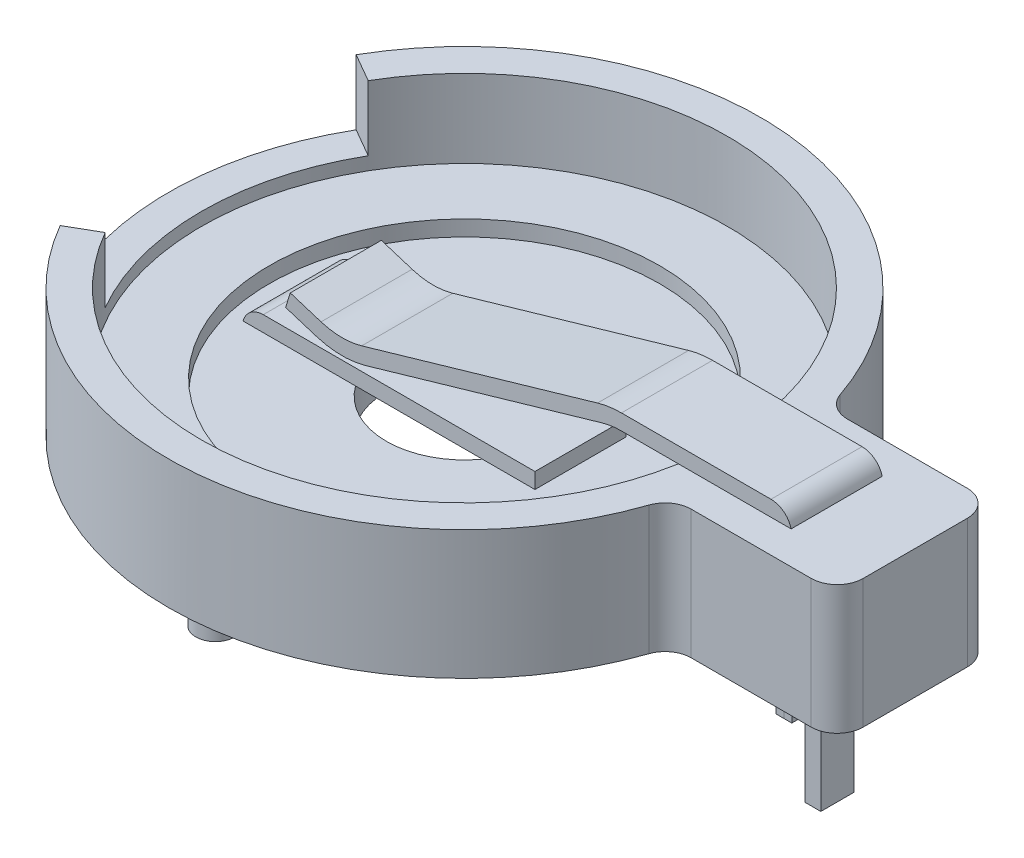
SolidWorks part; units mm, degrees
ref_plane "Front" through (0, 0, 0) normal (0, 0, 1) x (1, 0, 0)
ref_plane "Top" through (0, 0, 0) normal (0, 1, 0) x (1, 0, 0)
ref_plane "Right" through (0, 0, 0) normal (1, 0, 0) x (0, 0, -1)
sketch "Эскиз1" plane through (0, 0, 0) normal (0, 1, 0) x (1, 0, 0)
  line L0 (-11.375, 0) -> (17.5213, 0) construction
  line L1 (11.7107, 3) -> (16.325, 3)
  line L2 (11.7107, -3) -> (16.325, -3)
  line L3 (17.325, 2) -> (17.325, -2)
  arc A0 (16.325, 3) -> (17.325, 2) centre (16.325, 2) cw
  arc A2 (10.7644, 3.6768) -> (10.7644, -3.6768) centre (0, 0) ccw
  arc A3 (16.325, -3) -> (17.325, -2) centre (16.325, -2) ccw
  arc A4 (11.7107, 3) -> (10.7644, 3.6768) centre (11.7107, 4) cw
  arc A5 (11.7107, -3) -> (10.7644, -3.6768) centre (11.7107, -4) ccw
  point P11 (17.325, 3)
  point P14 (17.325, -3)
  point P17 (10.9723, 3)
  point P20 (10.9723, -3)
  dimension "D1" = 11.375
  dimension "D5" = 1
  dimension "D3" = 6
  dimension "D4" = 28.7
extrude "Вытянуть1" add sketch "Эскиз1" along normal blind 4.95
sketch "Эскиз2" plane through (0, 4.95, 0) normal (0, 1, 0) x (-1, 0, 0)
  circle A0 centre (0, 0) radius 10.11
  dimension "D1" = 20.22
extrude "Вырез-Вытянуть1" cut sketch "Эскиз2" against normal blind 3
sketch "Эскиз3" plane through (0, 4.95, 0) normal (0, 1, 0) x (-1, 0, 0)
  line L0 (0, 0) -> (11.375, 0) construction
  line L1 (0, 0) -> (11.3365, -6.5451) construction
  line L2 (0, 0) -> (11.3365, 6.5451) construction
  line L3 (8.7555, -5.055) -> (9.851, -5.6875)
  line L4 (9.851, 5.6875) -> (8.7555, 5.055)
  arc A0 (-10.7644, -3.6768) -> (-10.7644, 3.6768) centre (0, 0) ccw construction
  arc A1 (8.7555, 5.055) -> (8.7555, -5.055) centre (0, 0) cw
  circle A2 centre (0, 0) radius 10.11 construction
  arc A3 (9.851, 5.6875) -> (9.851, -5.6875) centre (0, 0) cw
  dimension "D1" = 30
extrude "Вырез-Вытянуть2" cut sketch "Эскиз3" against normal blind 2.5
sketch "Эскиз4" plane through (0, 1.95, 0) normal (0, 1, 0) x (-1, 0, 0)
  circle A0 centre (0, 0) radius 7.5
  dimension "D1" = 15
extrude "Вырез-Вытянуть3" cut sketch "Эскиз4" against normal blind 0.6
sketch "Эскиз5" plane through (0, 1.35, 0) normal (0, 1, 0) x (-1, 0, 0)
  circle A0 centre (0, 0) radius 3
extrude "Вырез-Вытянуть4" cut sketch "Эскиз5" against normal up to next
ref_plane "Плоскость1" through (0, 0, 0) normal (0, 0, 1) x (1, 0, 0)
sketch "Эскиз7" plane through (0, 0, 0) normal (0, 0, 1) x (1, 0, 0)
  line L0 (-7.9171, 1.65) -> (-0.6324, 1.65) construction
  line L1 (7.5, 1.35) -> (-7.5, 1.35) construction
  line L2 (-6.4821, 1.15) -> (-6.4821, -5)
  line L4 (-5.9821, 1.65) -> (4.4584, 1.65)
  line L6 (-11.375, 0) -> (10.7644, 0) construction
  arc A0 (-6.4821, 1.15) -> (-5.9821, 1.65) centre (-5.9821, 1.15) cw
  point P12 (-6.4821, 1.65)
  dimension "D3" = 0.5
  dimension "D1" = 5
  dimension "D2" = 0.3
ref_plane "Плоскость2" through (4.4584, 0, 0) normal (1, 0, 0) x (0, 0, -1)
sketch "Эскиз8" plane through (4.4584, 0, 0) normal (1, 0, 0) x (0, 0, -1)
  line L0 (-1.75, 1.95) -> (1.75, 1.95)
  line L1 (-1.75, 1.95) -> (-1.75, 1.35)
  line L2 (7.5, 1.95) -> (-7.5, 1.95) construction
  line L3 (3, 1.35) -> (-3, 1.35) construction
  line L4 (0, 7.1854) -> (0, -7.1854) construction
  line L6 (10.11, 1.95) -> (-10.11, 1.95) construction
  line L7 (-1.75, 1.35) -> (1.75, 1.35)
  line L8 (0, 2.6946) -> (0, 0.3193) construction
  line L9 (0, 1.15) -> (0, -5) construction
  line L10 (1.75, 1.95) -> (1.75, 1.35)
  point P18 (0, 1.35)
  point P19 (0, 1.95)
  dimension "D1" = 1.75
sweep "По траектории2" add profiles "Эскиз8" path "Эскиз7"
sketch "Эскиз9" plane through (0, 0, 0) normal (0, -1, 0) x (1, 0, 0)
  line L0 (0, 11.375) -> (0, 0) construction
  line L1 (0, 0) -> (9.851, -5.6875) construction
  line L2 (0, 0) -> (-9.851, -5.6875) construction
  arc A0 (10.7644, 3.6768) -> (10.7644, -3.6768) centre (0, 0) ccw construction
  circle A1 centre (0, 0) radius 9.575 construction
  circle A2 centre (0, 9.575) radius 0.75
  circle A3 centre (8.2922, -4.7875) radius 0.75
  circle A4 centre (-8.2922, -4.7875) radius 0.75
  dimension "D3" = 1.8
  dimension "D1" = 120
  dimension "D2" = 120
extrude "Вытянуть2" add sketch "Эскиз9" along normal blind 1.5
sketch "Эскиз10" plane through (0, -5, 0) normal (0, -1, 0) x (1, 0, 0)
  line L0 (-6.7821, 0) -> (-6.1821, 0) construction
  line L1 (-6.7821, -1.75) -> (-6.7821, 1.75) construction
  line L2 (-6.1821, 1.75) -> (-6.1821, -1.75) construction
  line L3 (-6.7821, 1.75) -> (-6.7821, 0.635)
  line L4 (-6.7821, -1.75) -> (-6.1821, -1.75)
  line L5 (-6.7821, -1.75) -> (-6.7821, -0.635)
  line L6 (-6.7821, -0.635) -> (-6.1821, -0.635)
  line L7 (-6.1821, -1.75) -> (-6.1821, -0.635)
  line L8 (-6.7821, 1.75) -> (-6.1821, 1.75)
  line L9 (-6.1821, 1.75) -> (-6.1821, 0.635)
  line L10 (-6.7821, 0.635) -> (-6.1821, 0.635)
  dimension "D1" = 1.27
extrude "Вырез-Вытянуть5" cut sketch "Эскиз10" against normal blind 3.5
ref_plane "Плоскость3" through (0, -5, 0) normal (0, -1, 0) x (1, 0, 0)
sketch "Эскиз12" plane through (0, 0, 0) normal (0, 0, 1) x (1, 0, 0)
  line L0 (14.0179, 0) -> (14.0179, 4.75)
  line L1 (11.7107, 4.95) -> (16.325, 4.95) construction
  line L2 (13.5179, 5.25) -> (7.7703, 5.25)
  line L3 (-6.4022, 2.25) -> (2.5235, 2.25) construction
  line L4 (-5.9821, 1.95) -> (4.4584, 1.95) construction
  line L5 (6.9347, 5.1313) -> (-2.1288, 2.5027)
  line L6 (-3.8652, 2.5223) -> (-5.0477, 2.8946)
  line L7 (11.7107, 0) -> (16.325, 0) construction
  arc A0 (7.7703, 5.25) -> (6.9347, 5.1313) centre (7.7703, 2.25) ccw
  arc A1 (-2.1288, 2.5027) -> (-3.8652, 2.5223) centre (-2.9645, 5.3839) cw
  arc A2 (14.0179, 4.75) -> (13.5179, 5.25) centre (13.5179, 4.75) ccw
  point P16 (-3, 2.25)
  point P19 (14.0179, 5.25)
  dimension "D3" = 3
  dimension "D4" = 3
  dimension "D5" = 0.5
  dimension "D1" = 0.3
  dimension "D2" = 0.3
sketch "Эскиз14" plane through (0, 0, 0) normal (0, -1, 0) x (1, 0, 0)
  line L0 (14.0179, 2.4013) -> (14.0179, -2.4345) construction
  line L1 (16.834, -0.0123) -> (11.3962, -0.0123) construction
  line L2 (14.3179, -1.7623) -> (14.3179, 1.7377)
  line L3 (14.3179, 1.7377) -> (14.0179, 1.7377)
  line L4 (14.3179, -1.7623) -> (14.0179, -1.7623)
  line L5 (14.0179, 1.7377) -> (13.7179, 1.7377)
  line L6 (14.0179, -1.7623) -> (13.7179, -1.7623)
  line L7 (13.7179, 1.7377) -> (13.7179, -1.7623)
  point P8 (14.3179, -0.0123)
  point P12 (13.7179, -0.0123)
  dimension "D1" = 3.5
  dimension "D2" = 0.3
  dimension "D3" = 0.3
sweep "По траектории3" add profiles "Эскиз14" path "Эскиз12"
sketch "Эскиз15" plane through (0, 0, 0) normal (0, 0, 1) x (1, 0, 0)
  line L0 (14.0179, 0) -> (14.0179, -1.5)
  line L2 (11.7107, 0) -> (16.325, 0) construction
  dimension "D1" = 1.5
sweep "По траектории4" add profiles "Эскиз14<3>" path "Эскиз15"
sketch "Эскиз14<3>" plane through (0, 0, 0) normal (0, -1, 0) x (1, 0, 0) same geometry as "Эскиз14"
sketch "Эскиз16" plane through (0, -1.5, 0) normal (0, -1, 0) x (1, 0, 0)
  line L0 (14.3179, -0.0123) -> (13.7179, -0.0123) construction
  line L1 (14.3179, -1.7623) -> (14.3179, 1.7377) construction
  line L2 (13.7179, 1.7377) -> (13.7179, -1.7623) construction
  line L3 (14.3179, 0.6227) -> (14.3179, -0.6473)
  line L4 (14.3179, -0.6473) -> (13.7179, -0.6473)
  line L5 (14.3179, 0.6227) -> (13.7179, 0.6227)
  line L6 (13.7179, -0.6473) -> (13.7179, 0.6227)
  dimension "D1" = 1.27
extrude "Вытянуть3" add sketch "Эскиз16" along normal blind 3.5
